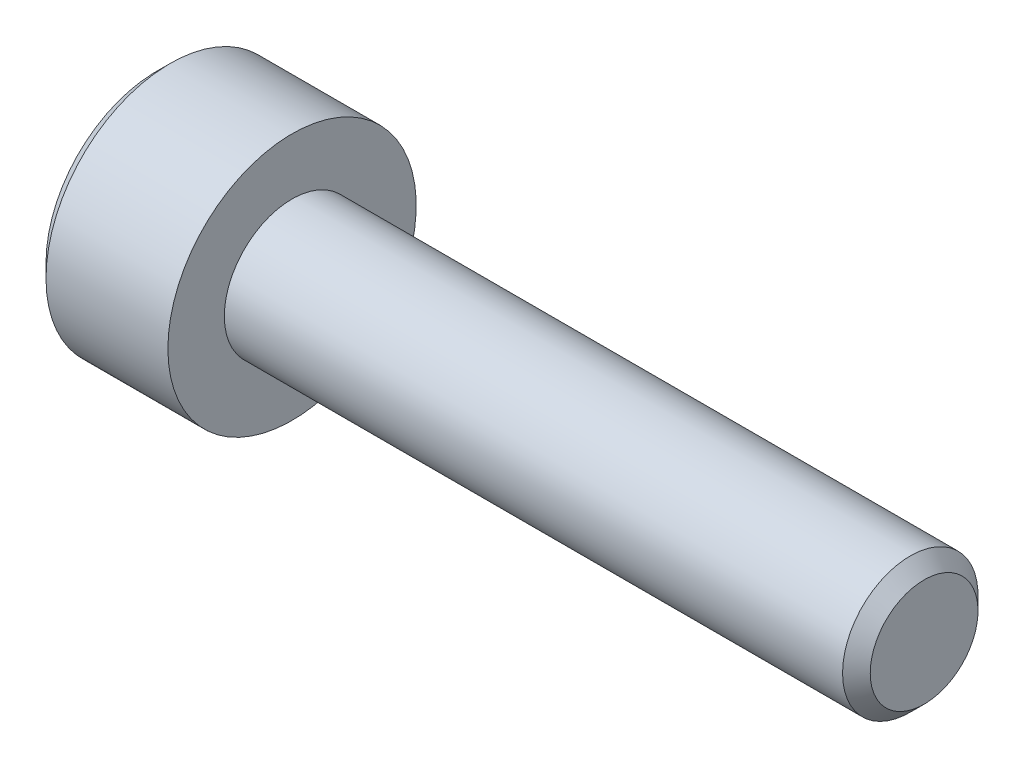
SolidWorks part; units mm, degrees
ref_plane "Front Plane" through (0, 0, 0) normal (0, 0, 1) x (1, 0, 0)
ref_plane "Top Plane" through (0, 0, 0) normal (0, 1, 0) x (1, 0, 0)
ref_plane "Right Plane" through (0, 0, 0) normal (1, 0, 0) x (0, 0, -1)
ref_plane "Plane1" through (1, 0, 0) normal (1, 0, 0) x (0, 0, -1)
ref_axis "Axis_X" through (-3.85, 0, 0) along (1, 0, 0)
ref_axis "Axis_Y" through (0, 3.025, 0) along (0, -1, 0)
ref_axis "Axis_Z" through (0, 0, -3.025) along (0, 0, 1)
sketch "Sketch1" plane through (0, 0, 0) normal (0, 0, 1) x (1, 0, 0)
  line L0 (-3, 0) -> (14, 0)
  line L1 (14, 0) -> (14, -1.1935)
  line L2 (14, -1.1935) -> (13.6935, -1.5)
  line L3 (13.6935, -1.5) -> (0, -1.5)
  line L4 (0, -1.5) -> (0, -2.75)
  line L5 (0, -2.75) -> (-2.7, -2.75)
  line L6 (-2.7, -2.75) -> (-3, -2.45)
  line L7 (-3, -2.45) -> (-3, 0)
  line L8 (0, 0) -> (-3, 0) construction
  line L9 (14, 1.1935) -> (13.6935, 1.5) construction
  line L10 (-3, 2.45) -> (-2.7, 2.75) construction
  point P16 (13.5, -1.5)
  dimension "A" = 5.5
  dimension "E" = 3
  dimension "MSM_1" = 2.387
  dimension "MSM_2" = 45
  dimension "MSM_3" = 0.3
  dimension "L" = 14
  dimension "Pitch_1" = 0.5
revolve "Revolve1" add sketch "Sketch1" angle 360 about axis through (-3.85, 0, 0) along (1, 0, 0)
sketch "Sketch2" plane through (-3, 0, 0) normal (-1, 0, 0) x (0, 0, 1)
  line L1 (0, 1.4434) -> (-1.25, 0.7217)
  line L2 (-1.25, 0.7217) -> (-1.25, -0.7217)
  line L3 (-1.25, -0.7217) -> (0, -1.4434)
  line L4 (0, -1.4434) -> (1.25, -0.7217)
  line L5 (1.25, -0.7217) -> (1.25, 0.7217)
  line L6 (1.25, 0.7217) -> (0, 1.4434)
  circle A0 centre (0, 0) radius 1.25 construction
  dimension "B" = 2.5
extrude "Cut-Extrude1" cut sketch "Sketch2" against normal blind 1.5
ref_plane "Dim. B_s" through (14, 0, 0) normal (1, 0, 0) x (0, 0, -1)
sketch "Sketch3" plane through (0, 0, 0) normal (0, 0, 1) x (1, 0, 0)
  line L0 (0, 0) -> (14, 0) construction
  line L1 (14, -1.3128) -> (14, 1.3128) construction
  line L3 (13.99, 1.5) -> (14, 1.5)
  line L5 (13.99, 1.5) -> (13.99, 1.49)
  line L6 (13.99, 1.49) -> (14, 1.49)
  line L7 (14, 1.5) -> (14, 1.49)
  line L8 (11, 1.5) -> (11.01, 1.5)
  line L9 (11, 1.5) -> (11, 1.49)
  line L10 (11, 1.49) -> (11.01, 1.49)
  line L11 (11.01, 1.5) -> (11.01, 1.49)
  dimension "MSM_5" = 0.01
  dimension "A_s" = 3
revolve "Cut-Revolve1" [suppressed] cut sketch "Sketch3" angle 360 about L0
equation "\"Factor\"= 1.082532"
equation "\"ATD_1\"= 4.134"
equation "\"L_s\"= 10"
equation "\"L_s\"= IIF ( ( \"M\" = 12 and \"L\" > 50 ) , 36 , IIF ( ( \"M\" = 10 and \"L\" > 40 ) , 32 , IIF ( ( \"M\" = 8 and \"L\" > 35 ) , 28 , IIF ( ( \"M\" = 6 and \"L\" > 30 ) , 24 , IIF ( ( \"M\" = 5 and \"L\" > 25 ) , 22 , IIF ( ( \"M\" = 4 and \"L\" > 25 ) , 20 , IIF ( ( \"M\" = 3 and \"L\" > 20 ) , 18 , \"L\" ) ) ) ) ) ) )"
equation "\"A\"= IIF ( \"M\" = 12 , 18 , IIF ( \"M\" = 10 , 16 , IIF ( \"M\" = 8 , 13 , IIF ( \"M\" = 6 , 10 , IIF ( \"M\" = 5 , 8.5 , IIF ( \"M\" = 4 , 7 , IIF ( \"M\" = 3 , 5.5 , IIF ( \"M\" = 2.6 or \"M\" = 2.5 , 4.5 , 3.8 ) ) ) ) ) ) ) )"
equation "\"E\"= \"M\""
equation "\"B\"= IIF ( \"M\" = 12 , 10 , IIF ( \"M\" = 10 , 8 , IIF ( \"M\" = 8 , 6 , IIF ( \"M\" = 6 , 5 , IIF ( \"M\" = 5 , 4 , IIF ( \"M\" = 4 , 3 , IIF ( \"M\" = 3 , 2.5 , IIF ( \"M\" = 2.6 or \"M\" = 2.5 , 2 , 1.5 ) ) ) ) ) ) ) )"
equation "\"MSM_4\"= \"M\" * 0.5"
equation "\"MSM_1\"= IIF ( \"M\" = 12 , 9.853 , IIF ( \"M\" = 10 , 8.16 , IIF ( \"M\" = 8 , 6.466 , IIF ( \"M\" = 6 , 4.773 , IIF ( \"M\" = 5 , 4.019 , IIF ( \"M\" = 4 , 3.141 , IIF ( \"M\" = 3 , 2.387 , IIF ( \"M\" = 2.6 , 2.048 , IIF ( \"M\" = 2.5 , 1.948 , 1.509 ) ) ) ) ) ) ) ) )"
equation "\"MSM_2\"= 45"
equation "\"MSM_3\"= IIF ( \"M\" = 2.6 , 0.26 , \"E\" * 0.1 )"
equation "\"Thread1\" = IIF ( ( ( \"M\" = 12 ) and ( \"L\" > 50 ) ) or ( ( \"M\" = 10 ) and ( \"L\" > 40 ) ) or ( ( \"M\" = 8 ) and ( \"L\" > 35 ) ) or ( ( \"M\" = 6 ) and ( \"L\" > 30 ) ) or ( ( \"M\" = 5 ) and ( \"L\" > 25 ) ) or ( ( \"M\" = 4 ) and ( \"L\" > 25 ) ) or ( \"M\" = 3 ) and ( \"L\" > 2 ) , \"suppressed\" , \"unsuppressed\" )"
equation "\"Thread2\" = IIF ( ( ( \"M\" = 12 ) and ( \"L\" > 50 ) ) or ( ( \"M\" = 10 ) and ( \"L\" > 40 ) ) or ( ( \"M\" = 8 ) and ( \"L\" > 35 ) ) or ( ( \"M\" = 6 ) and ( \"L\" > 30 ) ) or ( ( \"M\" = 5 ) and ( \"L\" > 25 ) ) or ( ( \"M\" = 4 ) and ( \"L\" > 25 ) ) or ( \"M\" = 3 ) and ( \"L\" > 2 ) , \"unsuppressed\" , \"suppressed\" )"
equation "\"MSM_5\"= 0.01"
equation "\"Cut-Revolve1\"= IIF ( \"TYP\" = 2 , \"unsuppressed\" , \"suppressed\" )"
equation "\"Pitch_1\"= IIF ( \"M\" = 12 , 1.75 , IIF ( \"M\" = 10 , 1.5 , IIF ( \"M\" = 8 , 1.25 , IIF ( \"M\" = 6 , 1 , IIF ( \"M\" = 5 , 0.8 , IIF ( \"M\" = 4 , 0.7 , IIF ( \"M\" = 3 , 0.5 , IIF ( \"M\" = 2.6 or \"M\" = 2.5 , 0.45 , 0.4 ) ) ) ) ) ) ) )"
equation "\"ATD_2\"= round ( \"M\" - \"Factor\" * \"Pitch_1\" , 3 )"
